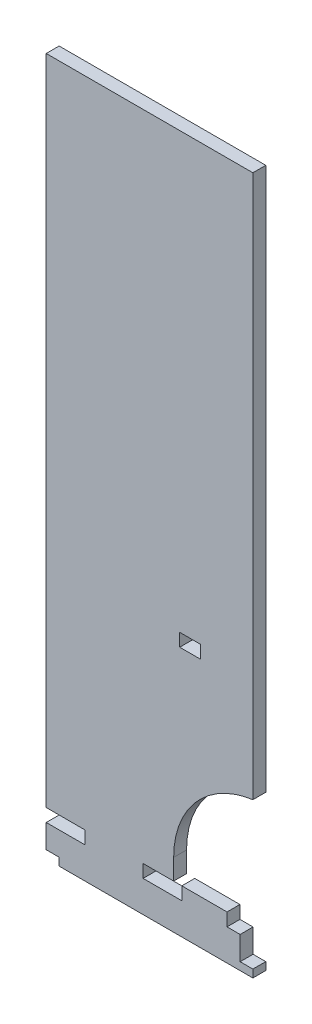
SolidWorks part; units mm, degrees
material "Balsa"
ref_plane "Plan de face" through (0, 0, 0) normal (0, 0, 1) x (1, 0, 0)
ref_plane "Plan de dessus" through (0, 0, 0) normal (0, 1, 0) x (1, 0, 0)
ref_plane "Plan de droite" through (0, 0, 0) normal (1, 0, 0) x (0, 0, -1)
sketch "Esquisse1" plane through (0, 0, 0) normal (0, 0, 1) x (1, 0, 0)
  line L0 (49.3309, 25.1093) -> (120.4109, 25.1093) construction
  line L1 (0, 0) -> (80, 0)
  line L2 (0, 0) -> (0, 270)
  line L3 (0, 270) -> (80, 270)
  line L4 (80, 59.7791) -> (80, 270)
  line L5 (49.3309, 25.1093) -> (49.3309, 17.15)
  line L6 (49.3309, 17.15) -> (80, 17.15)
  line L7 (80, 17.15) -> (80, 0)
  ellipse E0 centre (84.8709, 25.1093) end of major axis (120.4109, 25.1093) minor radius 35 (49.3309, 25.1093) -> (80, 59.7791) cw
  point P5 (84.8709, 25.1093)
  dimension "D1" = 80
  dimension "D2" = 270
  dimension "D3" = 80
  dimension "D4" = 70
  dimension "D5" = 71.08
extrude "Boss.-Extru.1" add sketch "Esquisse1" along normal blind 5
sketch "Esquisse2" plane through (0, 0, 5) normal (0, 0, 1) x (1, 0, 0)
  line L0 (80, 0) -> (80, 17.15) construction
  line L1 (51.6797, 101.7504) -> (59.6797, 101.7504)
  line L2 (51.6797, 101.7504) -> (51.6797, 96.7504)
  line L3 (51.6797, 96.7504) -> (59.6797, 96.7504)
  line L4 (59.6797, 101.7504) -> (59.6797, 96.7504)
  line L5 (75.08, 12.15) -> (70, 12.15)
  line L6 (80, 17.15) -> (80, 3)
  line L7 (80, 3) -> (75.08, 3)
  line L8 (75.08, 12.15) -> (75.08, 3)
  line L10 (0, 0) -> (80, 0) construction
  line L11 (70, 12.15) -> (70, 17.15)
  line L12 (80, 17.15) -> (49.3309, 17.15) construction
  line L13 (70, 17.15) -> (80, 17.15)
  line L14 (0, 270) -> (0, 0) construction
  line L15 (37.5, 17.15) -> (52.5, 17.15)
  line L16 (37.5, 17.15) -> (37.5, 12.15)
  line L17 (37.5, 12.15) -> (52.5, 12.15)
  line L18 (52.5, 17.15) -> (52.5, 12.15)
  line L19 (15, 17.15) -> (0, 17.15)
  line L20 (15, 17.15) -> (15, 12.15)
  line L21 (15, 12.15) -> (0, 12.15)
  line L22 (0, 17.15) -> (0, 12.15)
  line L24 (0, 0) -> (4.92, 0)
  line L25 (0, 0) -> (0, 3)
  line L26 (0, 3) -> (4.92, 3)
  line L27 (4.92, 0) -> (4.92, 3)
  dimension "D1" = 4.92
  dimension "D2" = 3
  dimension "D3" = 10
  dimension "D4" = 5
  dimension "D5" = 5
  dimension "D6" = 15
  dimension "D7" = 27.5
  dimension "D8" = 5
  dimension "D9" = 15
  dimension "D10" = 4.92
  dimension "D11" = 3
extrude "Enlèv. mat.-Extru.1" cut sketch "Esquisse2" against normal blind 5
